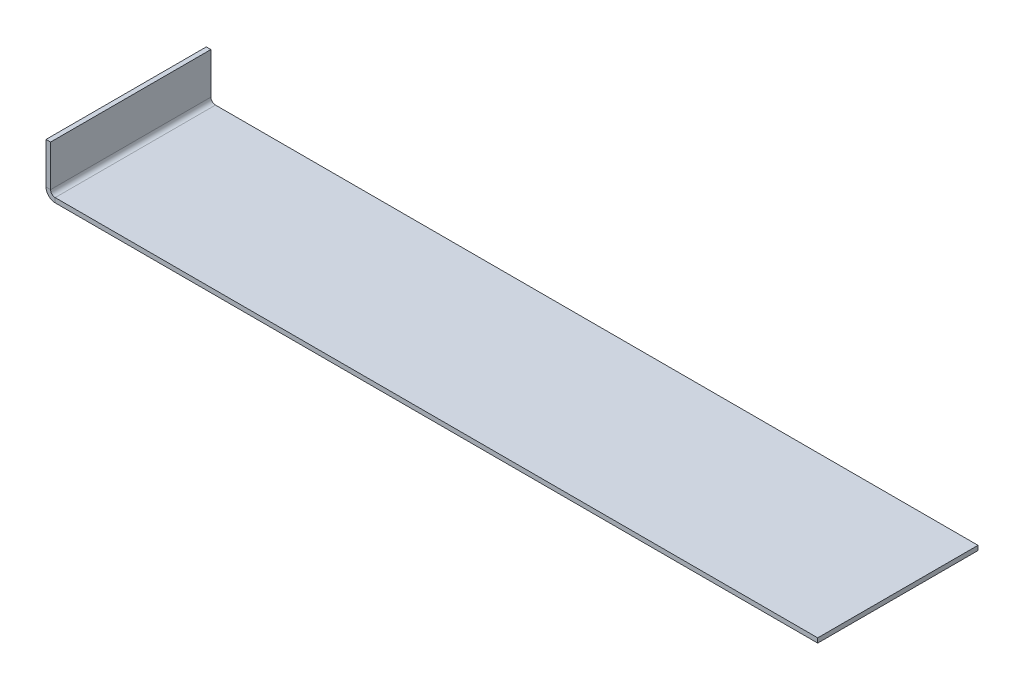
SolidWorks part; units mm, degrees
note: The reader was unsure of these and kept them because the rebuilt part matched: bend radius of "ﾍﾞｰｽﾍﾞﾝﾄﾞ1".
material "5052-H32"
ref_plane "正面" through (0, 0, 0) normal (0, 0, 1) x (1, 0, 0)
ref_plane "平面" through (0, 0, 0) normal (0, 1, 0) x (1, 0, 0)
ref_plane "右側面" through (0, 0, 0) normal (1, 0, 0) x (0, 0, -1)
sketch "ｽｹｯﾁ1" plane through (0, 0, 0) normal (0, 0, 1) x (1, 0, 0)
  line L0 (0, 20) -> (0, 0)
  line L1 (0, 0) -> (335, 0)
  dimension "D1" = 335
  dimension "D2" = 20
base flange "板金 ベースフランジ（タブ曲げ）" sketch "ｽｹｯﾁ1" end condition mid plane depth 70 reverse direction no thickness 2 reverse thickness direction no bend radius 2
bend "ﾍﾞｰｽﾍﾞﾝﾄﾞ1" bend radius 2 bend angle 90 parameters "D5"=1
sketch "ﾍﾞﾝﾄﾞ-ﾗｲﾝ1" [suppressed] plane through (0, 0, 0) normal (0, 1, 0) x (1, 0, 0)
sketch "境界ﾎﾞｯｸｽ1" [suppressed] plane through (0, 0, 0) normal (0, 1, 0) x (1, 0, 0)
sheet metal parameters "板金2" thickness 2 parameters "D1"=2
flat pattern "ﾌﾗｯﾄ-ﾊﾟﾀｰﾝ2" [suppressed]
sketch "ﾍﾞﾝﾄﾞ-ﾗｲﾝ2" plane through (0, 0, 0) normal (0, 1, 0) x (1, 0, 0)
  line L0 (-0.3562, -35) -> (-0.3562, 35) construction
  line L1 (-0.3562, -35) -> (-0.3562, 35) construction
sketch3d "境界ﾎﾞｯｸｽ2" [suppressed]
  line L0 (335, 0, 0) -> (-20.7124, 0, 0) construction
  line L1 (335, 70, 0) -> (-20.7124, 70, 0) construction
  line L2 (335, 0, 0) -> (335, 70, 0) construction
  line L3 (-20.7124, 0, 0) -> (-20.7124, 70, 0) construction
bend of the flat pattern "ﾌﾗｯﾄ-<ﾍﾞｰｽﾍﾞﾝﾄﾞ1>1"
equation "\"TRAY_LEN\" = 335"
equation "\"D1@ｽｹｯﾁ1\" = \"TRAY_LEN\""
equation "\"TRAY_TAB\" = 20"
equation "\"D2@ｽｹｯﾁ1\" = \"TRAY_TAB\""
